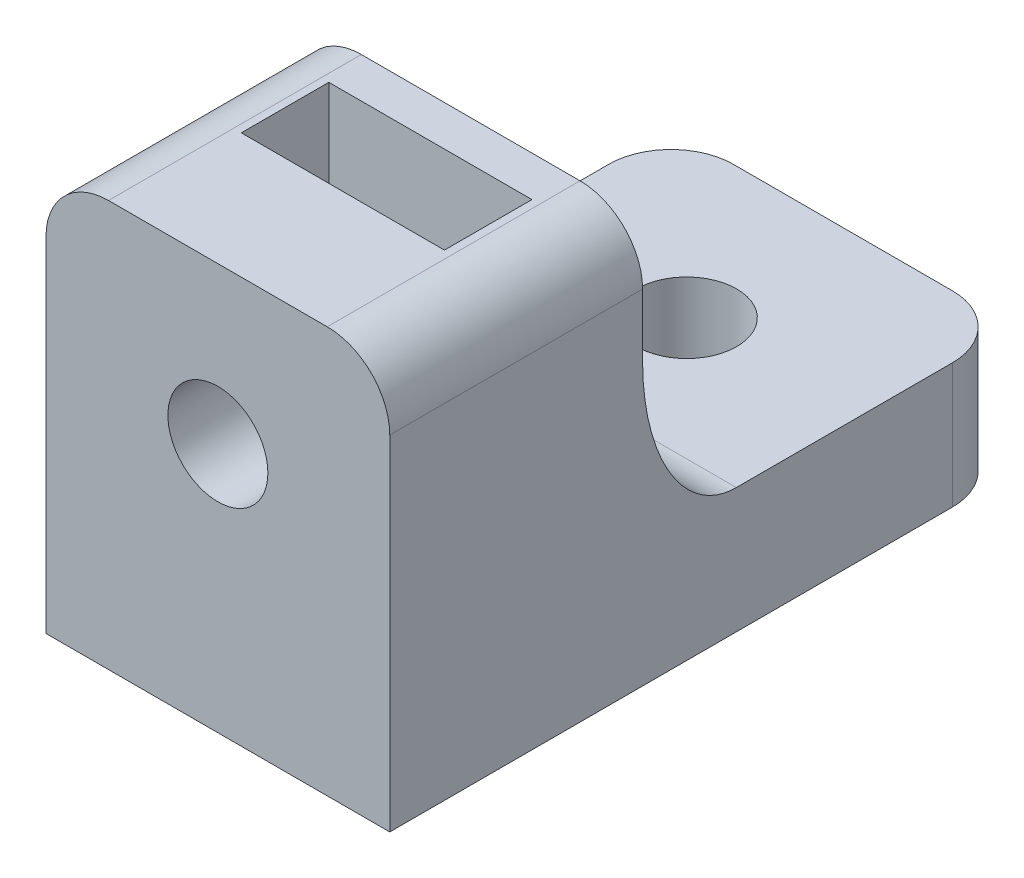
SolidWorks part; units mm, degrees
material "PET-G"
ref_plane "Front Plane" through (0, 0, 0) normal (0, 0, 1) x (1, 0, 0)
ref_plane "Top Plane" through (0, 0, 0) normal (0, 1, 0) x (1, 0, 0)
ref_plane "Right Plane" through (0, 0, 0) normal (1, 0, 0) x (0, 0, -1)
sketch "Sketch1" plane through (0, 0, 0) normal (0, 1, 0) x (1, 0, 0)
  line L0 (5.5, 8.09) -> (-5.5, 8.09)
  line L1 (-5.5, 0) -> (5.5, 0)
  line L2 (-5.5, 0) -> (-5.5, 20)
  line L3 (-5.5, 20) -> (5.5, 20)
  line L4 (5.5, 0) -> (5.5, 20)
  line L6 (3.25, 6.8) -> (-3.25, 6.8)
  line L7 (3.25, 6.8) -> (3.25, 4)
  line L8 (3.25, 4) -> (-3.25, 4)
  line L9 (-3.25, 6.8) -> (-3.25, 4)
  line L10 (3.25, 6.8) -> (-3.25, 4) construction
  line L11 (3.25, 4) -> (-3.25, 6.8) construction
  point P7 (0, 5.4)
  dimension "D1" = 11
  dimension "D2" = 20
  dimension "D3" = 2.8
  dimension "D4" = 4
  dimension "D5" = 6.5
extrude "Base" add sketch "Sketch1" along normal blind 4 contours L3 L4 L1 L2
extrude "VerticalPiece" add sketch "Sketch1<3>" along normal blind 13 contours L1 L4 L0 L2 L9 L6 L7 L8 region at (0, 0, -3.6966)
sketch "Sketch1<3>" plane through (0, 0, 0) normal (0, 1, 0) x (1, 0, 0) same geometry as "Sketch1"
fillet "FilletCorner" radius 3 1 edges at (0, 4, -8.09) second distance 5 first distance on face at (0, 4, -14.045)
hole_wizard "Ø3.2 (3.2) Horizontal Hole" positions "Sketch2" profile "Sketch4" hole size "Ø3.2" standard "ANSI Metric" end condition through all
sketch "Sketch2" plane through (0, 0, 0) normal (0, -1, 0) x (-1, 0, 0)
  line L0 (5.5, 0) -> (-5.5, 0) construction
  point P0 (0, 15)
  dimension "D1" = 15
sketch "Sketch4" plane through (0, 0, -15) normal (1, 0, 0) x (0, 0, -1)
  line L0 (0, 0) -> (0, 13)
  line L1 (0, 13) -> (1.6, 13)
  line L2 (1.6, 13) -> (1.6, 0)
  line L5 (1.6, 0) -> (0, 0)
  line L11 (0, -6.35) -> (0, 107.95) construction
  dimension "Thru Hole Dia." = 3.2
  dimension "Thru Hole Depth" = 13
hole_wizard "Ø3.2 (3.2) Vertical Hole" positions "Sketch5" profile "Sketch6" hole size "Ø3.2" standard "ANSI Metric" end condition through all
sketch "Sketch5" plane through (0, 0, 0) normal (0, 0, 1) x (1, 0, 0)
  line L0 (-5.5, 0) -> (5.5, 0) construction
  point P0 (0, 8)
  dimension "D1" = 8
sketch "Sketch6" plane through (0, 8, 0) normal (1, 0, 0) x (0, -1, 0)
  line L0 (0, 0) -> (0, 20)
  line L1 (0, 20) -> (1.6, 20)
  line L2 (1.6, 20) -> (1.6, 0)
  line L5 (1.6, 0) -> (0, 0)
  line L11 (0, -6.35) -> (0, 107.95) construction
  dimension "Thru Hole Dia." = 3.2
  dimension "Thru Hole Depth" = 20
extrude "NutSlot" add sketch "Sketch1<4>" along normal blind 4.8 contours L6 L9 L8 L7 region at (0, 0, -5.4)
sketch "Sketch1<4>" plane through (0, 0, 0) normal (0, 1, 0) x (1, 0, 0) same geometry as "Sketch1"
fillet "Fillet2" radius 2 4 edges at (5.5, 2, -20) (-5.5, 2, -20) (-5.5, 13, -4.045) (5.5, 13, -4.045)
fillet "ForReference" [suppressed] radius 0.4
